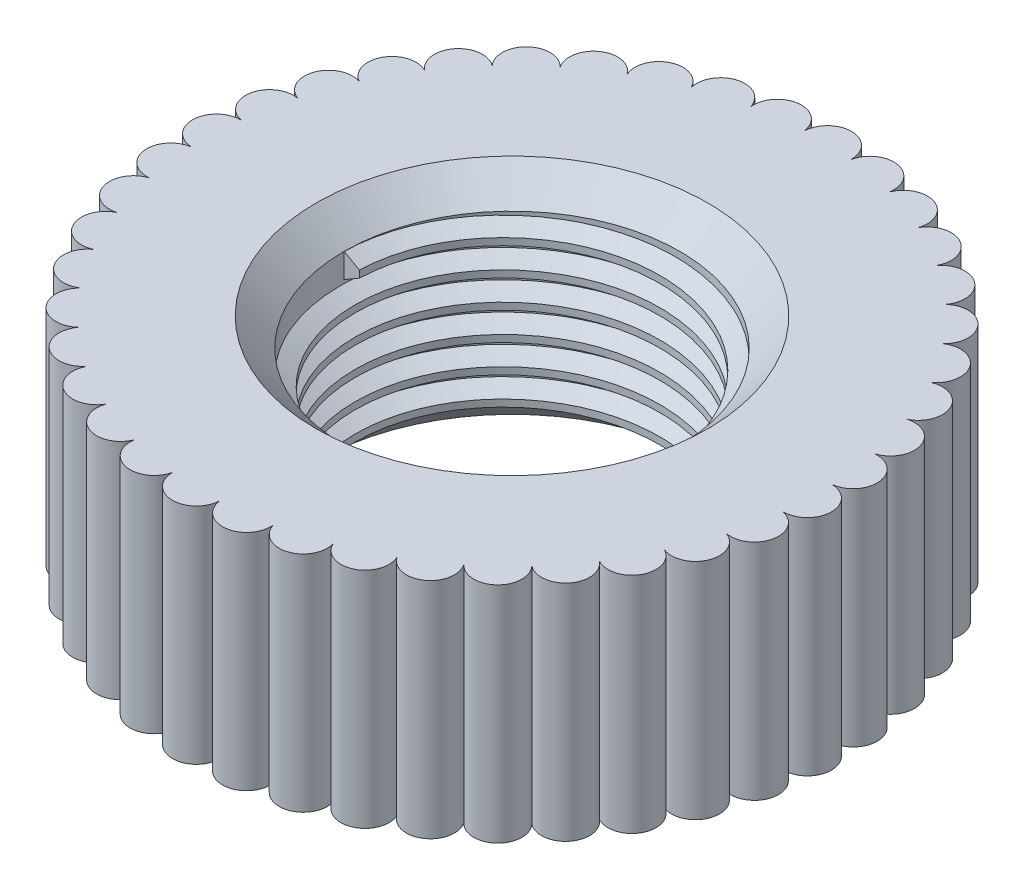
SolidWorks part; units mm, degrees
material "Латунь"
ref_plane "Спереди" through (0, 0, 0) normal (0, 0, 1) x (1, 0, 0)
ref_plane "Сверху" through (0, 0, 0) normal (0, 1, 0) x (1, 0, 0)
ref_plane "Справа" through (0, 0, 0) normal (1, 0, 0) x (0, 0, -1)
sketch "Эскиз1" plane through (0, 0, 0) normal (0, 1, 0) x (1, 0, 0)
  circle A0 centre (0, 0) radius 6
  circle A1 centre (0, 0) radius 3
extrude "Бобышка-Вытянуть1" add sketch "Эскиз1" along normal blind 4
chamfer "Фаска1" distance 0.5 angle 45 2 edges at (0, 0, 3) (0, 4, 3)
thread "Резьба1" pitch 0.5 start angle 0, offset 0, length 3, pitch 0.5, diameter 6
ref_plane "Плоскость2" through (-3, 3.5, 0) normal (0, 0, 1) x (-1, 0, 0)
sketch "Профиль резьбы2" plane through (-3, 3.5, 0) normal (0, 0, 1) x (-1, 0, 0)
  line L0 (0, 0) -> (0, 0.5) construction
  line L11 (0, 0) -> (0, 0.4375)
  line L12 (0, 0.4375) -> (-0.2706, 0.2812)
  line L13 (-0.2706, 0.2812) -> (-0.2706, 0.1562)
  line L15 (-0.2706, 0.1562) -> (0, 0)
  line L17 (-0.2706, 0.2187) -> (0, 0.2187) construction
  point P2 (0, 0)
  dimension "Pitch" = 0.5
  dimension "Profile_Angle" = 60
  dimension "Profile_Land" = 0.125
  dimension "Profile_Height" = 0.2706
sketch "Эскиз6" plane through (0, 4, 0) normal (0, 1, 0) x (1, 0, 0)
  line L1 (5.4482, -0.6092) -> (5.4764, 0.2506)
  line L2 (5.4764, 0.2506) -> (5.3698, 1.1042)
  line L3 (5.3698, 1.1042) -> (5.131, 1.9307)
  line L4 (5.131, 1.9307) -> (4.7658, 2.7095)
  line L5 (4.7658, 2.7095) -> (4.2832, 3.4217)
  line L6 (4.2832, 3.4217) -> (3.6952, 4.0496)
  line L7 (3.6952, 4.0496) -> (3.0162, 4.5778)
  line L8 (3.0162, 4.5778) -> (2.263, 4.9933)
  line L9 (2.263, 4.9933) -> (1.454, 5.2859)
  line L10 (1.454, 5.2859) -> (0.6092, 5.4482)
  line L11 (0.6092, 5.4482) -> (-0.2506, 5.4764)
  line L12 (-0.2506, 5.4764) -> (-1.1042, 5.3698)
  line L13 (-1.1042, 5.3698) -> (-1.9307, 5.131)
  line L14 (-1.9307, 5.131) -> (-2.7095, 4.7658)
  line L15 (-2.7095, 4.7658) -> (-3.4217, 4.2832)
  line L16 (-3.4217, 4.2832) -> (-4.0496, 3.6952)
  line L17 (-4.0496, 3.6952) -> (-4.5778, 3.0162)
  line L18 (-4.5778, 3.0162) -> (-4.9933, 2.263)
  line L19 (-4.9933, 2.263) -> (-5.2859, 1.454)
  line L20 (-5.2859, 1.454) -> (-5.4482, 0.6092)
  line L21 (-5.4482, 0.6092) -> (-5.4764, -0.2506)
  line L22 (-5.4764, -0.2506) -> (-5.3698, -1.1042)
  line L23 (-5.3698, -1.1042) -> (-5.131, -1.9307)
  line L24 (-5.131, -1.9307) -> (-4.7658, -2.7095)
  line L25 (-4.7658, -2.7095) -> (-4.2832, -3.4217)
  line L26 (-4.2832, -3.4217) -> (-3.6952, -4.0496)
  line L27 (-3.6952, -4.0496) -> (-3.0162, -4.5778)
  line L28 (-3.0162, -4.5778) -> (-2.263, -4.9933)
  line L29 (-2.263, -4.9933) -> (-1.454, -5.2859)
  line L30 (-1.454, -5.2859) -> (-0.6092, -5.4482)
  line L31 (-0.6092, -5.4482) -> (0.2506, -5.4764)
  line L32 (0.2506, -5.4764) -> (1.1042, -5.3698)
  line L33 (1.1042, -5.3698) -> (1.9307, -5.131)
  line L34 (1.9307, -5.131) -> (2.7095, -4.7658)
  line L35 (2.7095, -4.7658) -> (3.4217, -4.2832)
  line L36 (3.4217, -4.2832) -> (4.0496, -3.6952)
  line L37 (4.0496, -3.6952) -> (4.5778, -3.0162)
  line L38 (4.5778, -3.0162) -> (4.9933, -2.263)
  line L39 (4.9933, -2.263) -> (5.2859, -1.454)
  line L40 (5.2859, -1.454) -> (5.4482, -0.6092)
  circle A0 centre (0, 0) radius 5.4653 construction
  arc A1 (-1.1042, 5.3698) -> (-0.2506, 5.4764) centre (-0.6774, 5.4231) cw
  arc A2 (-0.2506, 5.4764) -> (0.6092, 5.4482) centre (0.1793, 5.4623) cw
  arc A3 (0.6092, 5.4482) -> (1.454, 5.2859) centre (1.0316, 5.367) cw
  arc A4 (1.454, 5.2859) -> (2.263, 4.9933) centre (1.8585, 5.1396) cw
  arc A5 (2.263, 4.9933) -> (3.0162, 4.5778) centre (2.6396, 4.7856) cw
  arc A6 (3.0162, 4.5778) -> (3.6952, 4.0496) centre (3.3557, 4.3137) cw
  arc A7 (3.6952, 4.0496) -> (4.2832, 3.4217) centre (3.9892, 3.7357) cw
  arc A8 (4.7658, 2.7095) -> (4.2832, 3.4217) centre (4.5245, 3.0656) ccw
  arc A9 (4.7658, 2.7095) -> (5.131, 1.9307) centre (4.9484, 2.3201) cw
  arc A10 (5.131, 1.9307) -> (5.3698, 1.1042) centre (5.2504, 1.5174) cw
  arc A11 (5.4764, 0.2506) -> (5.3698, 1.1042) centre (5.4231, 0.6774) ccw
  arc A12 (5.4764, 0.2506) -> (5.4482, -0.6092) centre (5.4623, -0.1793) cw
  arc A13 (5.4482, -0.6092) -> (5.2859, -1.454) centre (5.367, -1.0316) cw
  arc A14 (5.2859, -1.454) -> (4.9933, -2.263) centre (5.1396, -1.8585) cw
  arc A15 (4.9933, -2.263) -> (4.5778, -3.0162) centre (4.7856, -2.6396) cw
  arc A16 (4.5778, -3.0162) -> (4.0496, -3.6952) centre (4.3137, -3.3557) cw
  arc A17 (4.0496, -3.6952) -> (3.4217, -4.2832) centre (3.7357, -3.9892) cw
  arc A18 (3.4217, -4.2832) -> (2.7095, -4.7658) centre (3.0656, -4.5245) cw
  arc A19 (2.7095, -4.7658) -> (1.9307, -5.131) centre (2.3201, -4.9484) cw
  arc A20 (1.9307, -5.131) -> (1.1042, -5.3698) centre (1.5174, -5.2504) cw
  arc A21 (1.1042, -5.3698) -> (0.2506, -5.4764) centre (0.6774, -5.4231) cw
  arc A22 (0.2506, -5.4764) -> (-0.6092, -5.4482) centre (-0.1793, -5.4623) cw
  arc A23 (-0.6092, -5.4482) -> (-1.454, -5.2859) centre (-1.0316, -5.367) cw
  arc A24 (-1.454, -5.2859) -> (-2.263, -4.9933) centre (-1.8585, -5.1396) cw
  arc A25 (-2.263, -4.9933) -> (-3.0162, -4.5778) centre (-2.6396, -4.7856) cw
  arc A26 (-3.0162, -4.5778) -> (-3.6952, -4.0496) centre (-3.3557, -4.3137) cw
  arc A27 (-3.6952, -4.0496) -> (-4.2832, -3.4217) centre (-3.9892, -3.7357) cw
  arc A28 (-4.2832, -3.4217) -> (-4.7658, -2.7095) centre (-4.5245, -3.0656) cw
  arc A29 (-4.7658, -2.7095) -> (-5.131, -1.9307) centre (-4.9484, -2.3201) cw
  arc A30 (-5.131, -1.9307) -> (-5.3698, -1.1042) centre (-5.2504, -1.5174) cw
  arc A31 (-5.3698, -1.1042) -> (-5.4764, -0.2506) centre (-5.4231, -0.6774) cw
  arc A32 (-5.4764, -0.2506) -> (-5.4482, 0.6092) centre (-5.4623, 0.1793) cw
  arc A33 (-5.4482, 0.6092) -> (-5.2859, 1.454) centre (-5.367, 1.0316) cw
  arc A34 (-5.2859, 1.454) -> (-4.9933, 2.263) centre (-5.1396, 1.8585) cw
  arc A35 (-4.9933, 2.263) -> (-4.5778, 3.0162) centre (-4.7856, 2.6396) cw
  arc A36 (-4.5778, 3.0162) -> (-4.0496, 3.6952) centre (-4.3137, 3.3557) cw
  arc A37 (-4.0496, 3.6952) -> (-3.4217, 4.2832) centre (-3.7357, 3.9892) cw
  arc A38 (-3.4217, 4.2832) -> (-2.7095, 4.7658) centre (-3.0656, 4.5245) cw
  arc A39 (-1.9307, 5.131) -> (-2.7095, 4.7658) centre (-2.3201, 4.9484) ccw
  arc A40 (-1.9307, 5.131) -> (-1.1042, 5.3698) centre (-1.5174, 5.2504) cw
  circle M2 centre (0, 0) radius 6
extrude "Вырез-Вытянуть-Тонкостенный2" cut sketch "Эскиз6" against normal blind 10 thin contours A39 A40 A1 A2 A3 A4 A5 A6 A7 A8 A9 A10 A11 A12 A13 A14 A15 A16 A17 A18 A19 A20 A21 A22 A23 A24 A25 A26 A27 A28 A29 A30 A31 A32 A33 A34 A35 A36 A37 A38 M2
